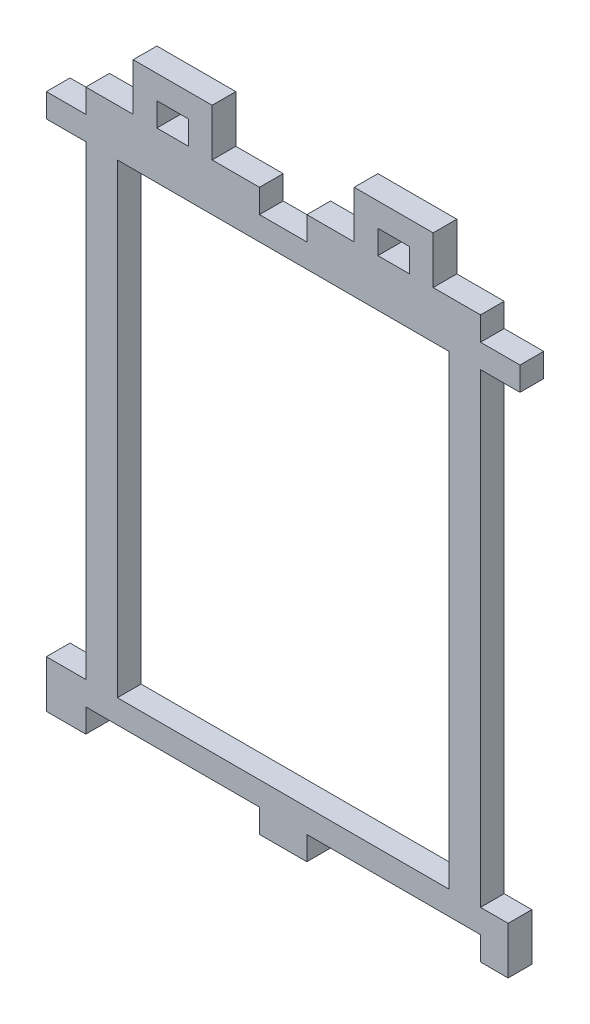
SolidWorks part; units mm, degrees
material "Custom Plastic"
ref_plane "Front Plane" through (0, 0, 0) normal (0, 0, 1) x (1, 0, 0)
ref_plane "Top Plane" through (0, 0, 0) normal (0, 1, 0) x (1, 0, 0)
ref_plane "Right Plane" through (0, 0, 0) normal (1, 0, 0) x (0, 0, -1)
sketch "Sketch1" plane through (0, 0, 0) normal (0, 0, 1) x (1, 0, 0)
  line L46 (0, 0) -> (5, 0)
  line L47 (5, 0) -> (5, 3)
  line L48 (5, 3) -> (27, 3)
  line L49 (27, 3) -> (27, 0)
  line L50 (27, 0) -> (33, 0)
  line L51 (33, 0) -> (33, 3)
  line L52 (33, 3) -> (55, 3)
  line L53 (55, 3) -> (55, 0)
  line L54 (55, 0) -> (60, 0)
  line L55 (60, 0) -> (60, -3)
  line L56 (60, -3) -> (55, -3)
  line L57 (55, -3) -> (55, -62)
  line L58 (55, -62) -> (58.5, -62)
  line L59 (58.5, -62) -> (58.5, -68)
  line L60 (58.5, -68) -> (55, -68)
  line L61 (55, -68) -> (55, -65)
  line L62 (55, -65) -> (33, -65)
  line L63 (33, -65) -> (33, -68)
  line L64 (33, -68) -> (27, -68)
  line L65 (27, -68) -> (27, -65)
  line L66 (27, -65) -> (5, -65)
  line L67 (5, -65) -> (5, -68)
  line L68 (5, -68) -> (0, -68)
  line L69 (0, -68) -> (0, -62)
  line L70 (0, -62) -> (5, -62)
  line L71 (0, 0) -> (0, -3)
  line L72 (0, -3) -> (5, -3)
  line L73 (5, -3) -> (5, -62)
  line L74 (9, -3) -> (9, -62)
  line L75 (9, -62) -> (51, -62)
  line L76 (51, -62) -> (51, -3)
  line L77 (51, -3) -> (9, -3)
  dimension "D10" = 5
  dimension "D11" = 3
  dimension "D12" = 22
  dimension "D13" = 6
  dimension "D14" = 22
  dimension "D15" = 5
  dimension "D16" = 3
  dimension "D17" = 59
  dimension "D18" = 6
  dimension "D19" = 3.5
  dimension "D20" = 3
  dimension "D21" = 22
  dimension "D22" = 6
  dimension "D23" = 4
  dimension "D24" = 4
extrude "Boss-Extrude1" add sketch "Sketch1" along normal blind 3
sketch "Sketch2" plane through (0, 0, 0) normal (0, 0, -1) x (-1, 0, 0)
  line L0 (-55, 3) -> (-33, 3) construction
  line L1 (-49, 3) -> (-39, 3)
  line L2 (-49, 3) -> (-49, 9)
  line L3 (-49, 9) -> (-39, 9)
  line L4 (-39, 3) -> (-39, 9)
  line L5 (-55, 0) -> (-55, 3) construction
  line L6 (-46, 3) -> (-42, 3)
  line L7 (-46, 3) -> (-46, 6)
  line L8 (-46, 6) -> (-42, 6)
  line L9 (-42, 3) -> (-42, 6)
  line L10 (-30, 0) -> (-30, 10.4595) construction
  line L11 (-33, 0) -> (-27, 0) construction
  line L12 (-18, 3) -> (-18, 6)
  line L13 (-14, 6) -> (-18, 6)
  line L14 (-14, 3) -> (-14, 6)
  line L15 (-14, 3) -> (-18, 3)
  line L16 (-21, 3) -> (-21, 9)
  line L17 (-11, 9) -> (-21, 9)
  line L18 (-11, 3) -> (-11, 9)
  line L19 (-11, 3) -> (-21, 3)
  line M13 (-5, 3) -> (-27, 3)
  line M17 (-33, 3) -> (-55, 3)
  dimension "D1" = 6
  dimension "D2" = 3
  dimension "D3" = 3
  dimension "D4" = 3
  dimension "D5" = 10
  dimension "D6" = 6
extrude "Boss-Extrude2" add sketch "Sketch2" against normal blind 3 contours L9 L4 L3 L2 L7 L8 M17 | L18 L17 L16 L12 L13 L14 M13 region at (44, 6.375, 0) region at (16, 6.375, 0)
